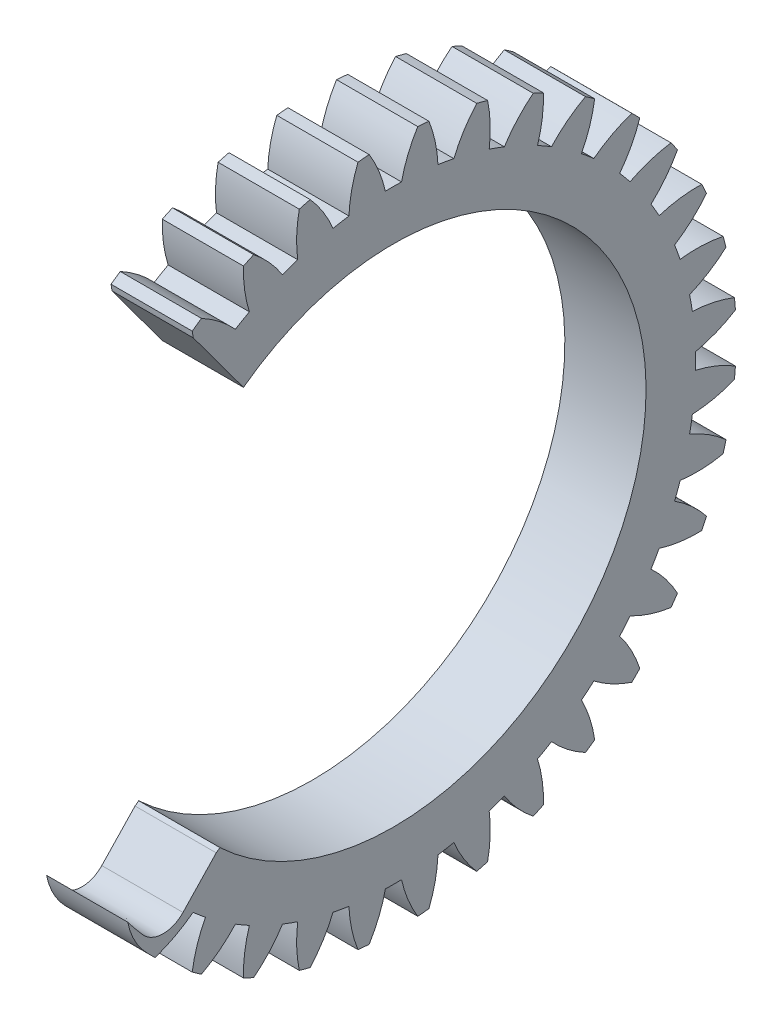
SolidWorks part; units mm, degrees
ref_plane "Plane1" through (0, 0, 0) normal (0, 0, 1) x (1, 0, 0)
ref_plane "Plane2" through (0, 0, 0) normal (0, 1, 0) x (1, 0, 0)
ref_plane "Plane3" through (0, 0, 0) normal (1, 0, 0) x (0, 0, -1)
sketch "HoldingSke" plane through (0, 0, 0) normal (0, 1, 0) x (1, 0, 0)
  line L0 (0, 0) -> (0.4045, -0.2939)
  line L1 (-15, 0) -> (100, 0) construction
  line L2 (0, 0) -> (-2.1039, 2.3779)
  line L3 (0, 0) -> (-11.863, 4.5341)
  line L4 (0, 0) -> (6.9867, 5.0761)
  line L5 (0, 0) -> (-46.8476, -17.4728)
  line L6 (0, 0) -> (-7.4607, -5.0337)
  line L7 (-2.1039, 2.3779) -> (8.6586, 51.2059)
  line L8 (-76.2, 54.61) -> (-71.9, 54.61)
  line L9 (-71.009, 38.7566) -> (-53.1078, 45.2721)
  line L10 (-76.2, 71.12) -> (104.1128, 71.12)
  line L11 (0, 0) -> (-9, 0)
  line L12 (-76.2, 101.6) -> (-76.133, 101.6)
  line L13 (24.9733, 27.94) -> (52.9518, 28.4284)
  line L14 (24.9733, 27.94) -> (24.9743, 27.94)
  line L15 (24.9733, 27.94) -> (100.4006, 29.5858)
  line L16 (-63.627, -2) -> (-12.827, -2)
  circle A0 centre (0, 0) radius 28
  circle A1 centre (0, 0) radius 33.499
  circle A2 centre (0, 0) radius 37.5
  circle A3 centre (0, 0) radius 28
  dimension "Num_teeth" = 36
  dimension "Pitch_radius" = 180.3128
  dimension "Width" = 9
  dimension "Thickness" = 9
sketch "BasProSke" plane through (0, 0, 0) normal (0, 1, 0) x (1, 0, 0)
  line L0 (-10, 0) -> (60, 0) construction
  line L1 (0, 0) -> (0, 38)
  line L2 (0, 0) -> (9, 0)
  line L3 (9, 0) -> (9, 38)
  line L4 (9, 38) -> (0, 38)
  dimension "Thickness" = 9
  dimension "Diameter" = 76
revolve "Base-Revolve" add sketch "BasProSke" angle 360 about L0
sketch "TooCutSke" plane through (0, 0, 0) normal (1, 0, 0) x (0, 0, -1)
  line L1 (0, 0) -> (0, 107) construction
  line L2 (0, 0) -> (-1.6875, 35.9604) construction
  line L3 (0, 0) -> (-6.2701, 71.6676) construction
  line L4 (-1.6875, 35.9604) -> (-3.135, 35.8338) construction
  arc A0 (0.8949, 33.487) -> (-0.8949, 33.487) centre (0, 0) ccw
  arc A1 (2.7061, 37.929) -> (-2.7061, 37.929) centre (0, 0) ccw
  circle A2 centre (0, 0) radius 36 construction
  circle A3 centre (0, 0) radius 33.8289 construction
  arc A4 (-0.8949, 33.487) -> (-2.7061, 37.929) centre (-14.9484, 30.347) ccw
  arc A5 (2.7061, 37.929) -> (0.8949, 33.487) centre (14.9484, 30.347) ccw
extrude "ToothCut" cut sketch "TooCutSke" along normal through all
fillet "Breaks" [suppressed] radius 0.04 tangent propagation no
fillet "RootFillets" [suppressed] radius 0.501
pattern_circular "TeethCuts" count 36 every 10 about axis through (-10, 0, 0) along (1, 0, 0) of "ToothCut", "RootFillets", "Breaks"
sketch "HubNeaOneSke" plane through (0, 0, 0) normal (-1, 0, 0) x (0, 0, 1)
  circle A0 centre (0, 0) radius 33.499
  dimension "Diameter" = 66.998
extrude "HubNearOne" [suppressed] add sketch "HubNeaOneSke" along normal blind 41.0001
sketch "HubNeaBotSke" plane through (0, 0, 0) normal (-1, 0, 0) x (0, 0, 1)
  circle A0 centre (0, 0) radius 33.499
  dimension "Diameter" = 66.998
extrude "HubNearBoth" [suppressed] add sketch "HubNeaBotSke" along normal blind 20.5
ref_plane "FarPln" through (9, 0, 0) normal (1, 0, 0) x (0, 0, -1)
sketch "HubFarSke" plane through (9, 0, 0) normal (1, 0, 0) x (0, 0, -1)
  circle A0 centre (0, 0) radius 33.499
  dimension "Diameter" = 66.998
extrude "HubFar" [suppressed] add sketch "HubFarSke" along normal blind 20.5
sketch "BorSke" plane through (0, 0, 0) normal (1, 0, 0) x (0, 0, -1)
  circle A0 centre (0, 0) radius 28
  dimension "Diameter" = 56
extrude "Bore" cut sketch "BorSke" along normal mid plane 100.0001
sketch "KeySke" plane through (0, 0, 0) normal (1, 0, 0) x (0, 0, -1)
  line L0 (-8, 0) -> (-8, 32.3)
  line L1 (-8, 32.3) -> (8, 32.3)
  line L2 (8, 32.3) -> (8, 0)
  line L3 (0, 0) -> (0, 34) construction
  line L4 (-8, 0) -> (8, 0)
  dimension "Width" = 16
extrude "Keyway" [suppressed] cut sketch "KeySke" along normal mid plane 100.0001
pattern_circular "Keyway2" [suppressed] count 2 every 90 about axis through (-10, 0, 0) along (1, 0, 0) reverse direction yes
sketch "Szkic1" plane through (0, 0, 0) normal (1, 0, 0) x (0, 0, -1)
  line L0 (0, 0) -> (-27.328, 37.0259)
  line L1 (-27.328, 37.0259) -> (-47.6164, -10.233)
  line L2 (-47.6164, -10.233) -> (0, 0)
extrude "Wytnij-wyciągnięcie1" cut sketch "Szkic1" along normal through all
sketch "Szkic2" plane through (0, 0, 0) normal (1, 0, 0) x (0, 0, -1)
  line L0 (-19.6433, -20.6493) -> (-23.3286, -24.5233) construction
  line L1 (-19.6433, -20.6493) -> (-23.3286, -24.5233)
  line L2 (-24.5118, 27.7159) -> (-14.2182, -16.6493)
  line L3 (-14.2182, -16.6493) -> (-19.6433, -20.6493)
  line L4 (-24.5118, 27.7159) -> (-50.9594, 25.255)
  line L5 (-50.9594, 25.255) -> (-37.7356, -29.3697)
  line L6 (-37.7356, -29.3697) -> (-27.7664, -24.4546)
  line L7 (-26.426, -27.3069) -> (-27.3069, -26.426)
  line L8 (-26.426, -27.3069) -> (-25.0675, -25.4318)
  arc A0 (-24.5118, 27.7159) -> (-27.7664, -24.4546) centre (0, 0) ccw construction
  arc A1 (-24.5118, 27.7159) -> (-27.7664, -24.4546) centre (0, 0) ccw
  arc A2 (-27.3069, -26.426) -> (-29.4473, -22.4022) centre (-21.7924, -20.9115) cw
  spline S0 degree 3 poles (45009.463, 56084.8066) (2096.0635, 2871.4497) (-95.4614, 25.8215) (-27.1426, -24.9996) (-26.9606, -25.1074) (-26.5829, -25.2806) (-26.3868, -25.3469) (-25.9801, -25.4387) (-25.7711, -25.4633) (-25.3572, -25.469) (-25.1483, -25.4503) (-24.7384, -25.37) (-24.5404, -25.3094) (-24.158, -25.1482) (-23.9725, -25.0463) (51.1833, 26.9389) (-2343.5236, 3306.5474) (-43531.4014, 57286.5351) knots -51.138446 -51.138446 -51.138446 -51.138446 0.125 0.125 0.25 0.25 0.375 0.375 0.5 0.5 0.625 0.625 0.75 0.75 0.875 0.875 55.787982 55.787982 55.787982 55.787982 only from (-27.7664, -24.4546) to (-23.3286, -24.5233) construction
  spline S1 degree 3 poles (-27.7664, -24.4546) (-27.6277, -24.6121) (-27.4749, -24.7523) (-27.1426, -24.9996) (-26.9606, -25.1074) (-26.5829, -25.2806) (-26.3868, -25.3469) (-25.9801, -25.4387) (-25.7711, -25.4633) (-25.3572, -25.469) (-25.1483, -25.4503) (-24.7384, -25.37) (-24.5404, -25.3094) (-24.158, -25.1482) (-23.9725, -25.0463) (-23.6312, -24.8102) (-23.4733, -24.6754) (-23.3286, -24.5233) knots 0 0 0 0 0.125 0.125 0.25 0.25 0.375 0.375 0.5 0.5 0.625 0.625 0.75 0.75 0.875 0.875 1 1 1 1
extrude "Wytnij-wyciągnięcie2" cut sketch "Szkic2" against normal blind 43 and the other way through all contours A1 L4 L5 L6 | A1 S1 L1 L3 L2 region at (0, -1.5762, 26.5296) region at (0, 4.8425, 39.1923)
extrude "Dodanie-wyciągnięcie1" add sketch "Szkic2<3>" along normal up to surface (9 mm away) contours A2 L6 A1 | S1 L6 A2 L7 L8 region at (0, -25.7946, 26.8655) region at (0, -23.8723, 28.649) up to face at (9, -1.2954, -9.9994)
sketch "Szkic2<3>" plane through (0, 0, 0) normal (1, 0, 0) x (0, 0, -1) same geometry as "Szkic2"
equation "' \"Module@HoldingSke\" = 6.35"
equation "' \"Num_teeth@HoldingSke\" = 12"
equation "' \"Ap@HoldingSke\" =  20"
equation "' \"Ap@HoldingSke\" = 20"
equation "' \"Width@HoldingSke\" = 0.5 * 25.4"
equation "' \"Hub_dia@HoldingSke\"= 1 * 25.4"
equation "' \"Hub_dia@HoldingSke\" = 1 * 25.4"
equation "' \"Overall_len@HoldingSke\" = 1.0 * 25.4"
equation "' \"Bore@HoldingSke\" = 0.75 * 25.4"
equation "' \"T_dim@HoldingSke\" = 0.1 * 25.4"
equation "' \"Width@KeySke\" = 0.25 * 25.4"
equation "' \"Show_teeth@HoldingSke\" = 13"
equation "' \"Backlash@HoldingSke\" = 0.009 * 25.4"
equation "' \"Addendum_fac@HoldingSke\" = 1.0"
equation "' \"Dedendum_fac@HoldingSke\" = 1.25"
equation "' \"Dedendum_add@HoldingSke\" = 0.00005 * 25.4"
equation "' \"Clearance_fac@HoldingSke\" = 0.25"
equation "\"Pitch@HoldingSke\" = 1 / \"Module@HoldingSke\""
equation "\"Overcut_dia@TooCutSke\" = (\"Num_teeth@HoldingSke\" + 2 * \"Addendum_fac@HoldingSke\") / \"Pitch@HoldingSke\" + 0.002 * 25.4"
equation "\"Pitch_dia@TooCutSke\" = \"Num_teeth@HoldingSke\" / \"Pitch@HoldingSke\""
equation "\"Base_dia@TooCutSke\" = \"Num_teeth@HoldingSke\" / \"Pitch@HoldingSke\" * cos((\"Ap@HoldingSke\"  * 3.14159265 / 180))"
equation "\"Root_dia@TooCutSke\" = (\"Num_teeth@HoldingSke\" + 2) / \"Pitch@HoldingSke\" - 2 * (\"Addendum_fac@HoldingSke\" + \"Dedendum_fac@HoldingSke\") / \"Pitch@HoldingSke\" - \"Dedendum_add@HoldingSke\" * 2"
equation "\"Half_ang@TooCutSke\" = 180 / \"Num_teeth@HoldingSke\""
equation "\"Half_CT@TooCutSke\" = \"Num_teeth@HoldingSke\" / \"Pitch@HoldingSke\" * sin((3.14159265 / 2 / \"Num_teeth@HoldingSke\")) / 2 - 7 * \"Backlash@HoldingSke\" / 4"
equation "\"Flank_rad@TooCutSke\" = \"Num_teeth@HoldingSke\" / \"Pitch@HoldingSke\" / 5"
equation "\"Radius@RootFillets\" = \"Clearance_fac@HoldingSke\" / \"Pitch@HoldingSke\" + \"Dedendum_add@HoldingSke\""
equation "\"Break_rad@Breaks\" = 0.02 / \"Pitch@HoldingSke\""
equation "\"Thickness@HoldingSke\" = \"Width@HoldingSke\""
equation "\"OAL@HoldingSke\" = \"Thickness@HoldingSke\""
equation "\"MHD@HoldingSke\" = (\"Num_teeth@HoldingSke\" + 2) / \"Pitch@HoldingSke\" - 2 * (\"Addendum_fac@HoldingSke\" + \"Dedendum_fac@HoldingSke\")  / \"Pitch@HoldingSke\" - \"Dedendum_add@HoldingSke\" * 2"
equation "\"MBD@HoldingSke\" = (\"Num_teeth@HoldingSke\" + 2) / \"Pitch@HoldingSke\" - 2 * (\"Addendum_fac@HoldingSke\" + \"Dedendum_fac@HoldingSke\")  / \"Pitch@HoldingSke\" - \"Dedendum_add@HoldingSke\" * 2 - 0.002 * 25.4"
equation "\"MHD@HoldingSke\" = ((sgn( \"MHD@HoldingSke\" - \"Hub_dia@HoldingSke\" )-1)*( \"MHD@HoldingSke\" - \"Hub_dia@HoldingSke\" ))/-2+ \"Hub_dia@HoldingSke\""
equation "\"MBD@HoldingSke\" = ((sgn( \"MBD@HoldingSke\" - \"Bore@HoldingSke\" )-1)*( \"MBD@HoldingSke\" - \"Bore@HoldingSke\" ))/-2+ \"Bore@HoldingSke\""
equation "\"OAL@HoldingSke\" = ((sgn( \"OAL@HoldingSke\" - \"Overall_len@HoldingSke\" )+1)*( \"OAL@HoldingSke\" - \"Overall_len@HoldingSke\" ))/2 + \"Overall_len@HoldingSke\" + 0.000002 * 25.4"
equation "\"Num_teeth@TeethCuts\" = int( \"Show_teeth@HoldingSke\" ) + 1"
equation "\"Num_teeth@TeethCuts\" = ((sgn( \"Num_teeth@TeethCuts\" - \"Num_teeth@HoldingSke\" )-1)*( \"Num_teeth@TeethCuts\" - \"Num_teeth@HoldingSke\" ))/-2+ \"Num_teeth@HoldingSke\""
equation "\"Num_teeth@TeethCuts\" = ((sgn( \"Num_teeth@TeethCuts\" - 2.0)+1)*( \"Num_teeth@TeethCuts\" - 2.0))/2 +2.0"
equation "\"Angle@TeethCuts\" = 360.0 / \"Num_teeth@HoldingSke\""
equation "\"Diameter@BasProSke\" = (\"Num_teeth@HoldingSke\" + 2 * \"Addendum_fac@HoldingSke\") / \"Pitch@HoldingSke\""
equation "\"Thickness@BasProSke\"  = \"Thickness@HoldingSke\""
equation "' \"Fillet_rad@BasProSke\" =  \"Thickness@HoldingSke\" * 0.05"
equation "' \"Fillet_rad@BasProSke\" = \"Thickness@HoldingSke\" * 0.05"
equation "\"MHD@HoldingSke\" = ((sgn( \"MHD@HoldingSke\" - \"Root_dia@TooCutSke\" )-1)*( \"MHD@HoldingSke\" - \"Root_dia@TooCutSke\" ))/-2+ \"Root_dia@TooCutSke\""
equation "\"Diameter@HubNeaOneSke\" = \"MHD@HoldingSke\""
equation "\"Length@HubNearOne\" = \"OAL@HoldingSke\" - \"Thickness@BasProSke\""
equation "\"Diameter@HubNeaBotSke\" = \"MHD@HoldingSke\""
equation "\"Length@HubNearBoth\" = ( \"OAL@HoldingSke\" - \"Thickness@BasProSke\" ) / 2.0"
equation "\"Thickness@FarPln\" = \"Thickness@BasProSke\""
equation "\"Diameter@HubFarSke\" = \"MHD@HoldingSke\""
equation "\"Length@HubFar\" = ( \"OAL@HoldingSke\" - \"Thickness@BasProSke\" ) / 2.0"
equation "\"Diameter@BorSke\" = \"MBD@HoldingSke\""
equation "\"D1@Bore\" = \"OAL@HoldingSke\" * 2.0"
equation "\"D1@Keyway\" = \"OAL@HoldingSke\" * 2.0"
equation "\"Offset@KeySke\" = \"T_dim@HoldingSke\" + \"MBD@HoldingSke\" / 2.0"
